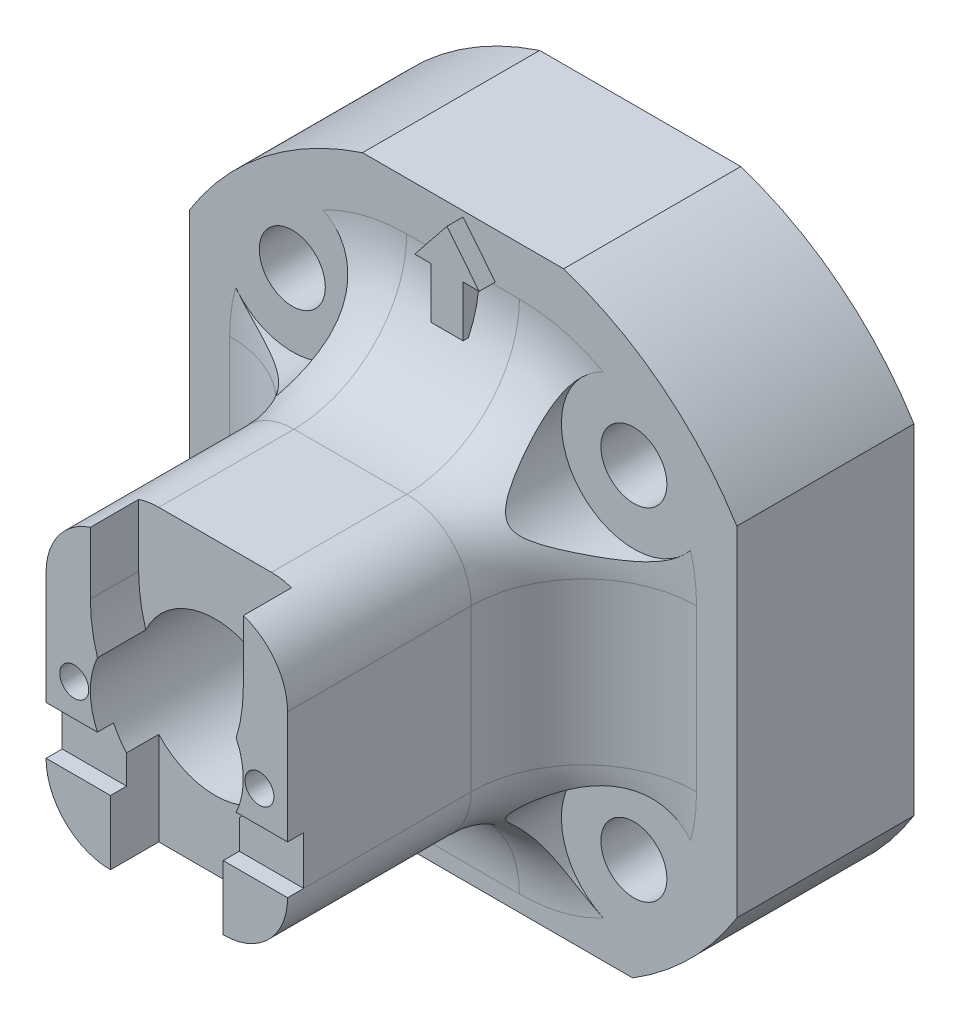
SolidWorks part; units mm, degrees
ref_plane "Front Plane" through (0, 0, 0) normal (0, 0, 1) x (1, 0, 0)
ref_plane "Top Plane" through (0, 0, 0) normal (0, 1, 0) x (1, 0, 0)
ref_plane "Right Plane" through (0, 0, 0) normal (1, 0, 0) x (0, 0, -1)
sketch "Sketch1" plane through (0, 0, 0) normal (0, 0, 1) x (1, 0, 0)
  circle A0 centre (0, 0) radius 20
  circle A1 centre (0, 0) radius 4.75
  dimension "D1" = 9.5
  dimension "D2" = 40
extrude "Boss-Extrude1" add sketch "Sketch1" along normal blind 11
sketch "Sketch2" plane through (0, 0, 11) normal (0, 0, 1) x (1, 0, 0)
  line L0 (0, 0) -> (0, 19) construction
  line L1 (-6.5933, 20) -> (6.5933, 20)
  line L2 (-6.5933, 20) -> (-6.5933, 19)
  line L3 (-6.5933, 19) -> (6.5933, 19)
  line L4 (6.5933, 20) -> (6.5933, 19)
  line L6 (-20, 15.8908) -> (-17, 15.8908)
  line L7 (-20, 15.8908) -> (-20, -10.5357)
  line L8 (-20, -10.5357) -> (-17, -10.5357)
  line L9 (-17, 15.8908) -> (-17, -10.5357)
  line L10 (20, 11.7256) -> (17, 11.7256)
  line L11 (20, 11.7256) -> (20, -14.8962)
  line L12 (20, -14.8962) -> (17, -14.8962)
  line L13 (17, 11.7256) -> (17, -14.8962)
  line L14 (19.7919, -20) -> (-18.9444, -20)
  line L15 (19.7919, -20) -> (19.7919, -17)
  line L16 (19.7919, -17) -> (-18.9444, -17)
  line L17 (-18.9444, -20) -> (-18.9444, -17)
  circle A0 centre (0, 0) radius 20 construction
  dimension "D1" = 1
  dimension "D2" = 3
extrude "Cut-Extrude1" cut sketch "Sketch2" against normal through all
sketch "Sketch3" plane through (0, 0, 11) normal (0, 0, 1) x (1, 0, 0)
  circle A0 centre (10.6066, -10.6066) radius 2 construction
  circle A1 centre (10.6066, 10.6066) radius 2 construction
  circle A2 centre (-10.6066, -10.6066) radius 2 construction
  circle A3 centre (-10.6066, 10.6066) radius 2 construction
  circle A4 centre (10.6066, -10.6066) radius 2 construction
  circle A5 centre (10.6066, 10.6066) radius 2 construction
  circle A6 centre (-10.6066, -10.6066) radius 2 construction
  circle A7 centre (-10.6066, 10.6066) radius 2 construction
  circle A8 centre (-10.6066, -10.6066) radius 2.05
  circle A9 centre (-10.6066, 10.6066) radius 2.05
  circle A10 centre (10.6066, 10.6066) radius 2.05
  circle A11 centre (10.6066, -10.6066) radius 2.05
  dimension "D1" = 4.1
extrude "Cut-Extrude2" cut sketch "Sketch3" against normal through all
sketch "Sketch5" plane through (0, 0, 11) normal (0, 0, 1) x (1, 0, 0)
  line L4 (7.5, -5) -> (7.5, 5)
  line L5 (3.5, 9) -> (-3.5, 9)
  line L6 (-7.5, 5) -> (-7.5, -5)
  line L7 (-3.5, -9) -> (3.5, -9)
  line L8 (7.5, -5) -> (7.5, 5)
  line L9 (3.5, 9) -> (-3.5, 9)
  line L10 (-7.5, 5) -> (-7.5, -5)
  line L11 (-3.5, -9) -> (3.5, -9)
  circle A0 centre (-5.75, 0) radius 1.075 construction
  circle A1 centre (5.75, 0) radius 1.075 construction
  circle A2 centre (-5.75, 0) radius 1.075 construction
  circle A3 centre (5.75, 0) radius 1.075 construction
  circle A4 centre (-5.75, 0) radius 0.9
  circle A5 centre (5.75, 0) radius 0.9
  arc A8 (3.5, -9) -> (7.5, -5) centre (3.5, -5) ccw
  arc A9 (7.5, 5) -> (3.5, 9) centre (3.5, 5) ccw
  arc A10 (-3.5, 9) -> (-7.5, 5) centre (-3.5, 5) ccw
  arc A11 (-7.5, -5) -> (-3.5, -9) centre (-3.5, -5) ccw
  arc A12 (3.5, -9) -> (7.5, -5) centre (3.5, -5) ccw
  arc A13 (7.5, 5) -> (3.5, 9) centre (3.5, 5) ccw
  arc A14 (-3.5, 9) -> (-7.5, 5) centre (-3.5, 5) ccw
  arc A15 (-7.5, -5) -> (-3.5, -9) centre (-3.5, -5) ccw
  dimension "D2" = 1.8
  dimension "D1" = 0
extrude "Boss-Extrude2" add sketch "Sketch5" along normal up to surface (18.4 mm away)
sketch "Sketch13" plane through (0, 0, 11) normal (0, 0, 1) x (1, 0, 0)
  circle A0 centre (5.75, 0) radius 0.9 construction
  circle A1 centre (-5.75, 0) radius 0.9 construction
  circle A2 centre (5.75, 0) radius 0.9
  circle A3 centre (-5.75, 0) radius 0.9
extrude "Boss-Extrude3" add sketch "Sketch13" along normal offset from surface (8.4 mm away) 10 up to face at (5.75, -0.9, 29.4)
sketch "Sketch7" plane through (0, 0, 29.4) normal (0, 0, 1) x (1, 0, 0)
  line L1 (-8.8438, -2) -> (9.3839, -2)
  line L2 (-8.8438, -2) -> (-8.8438, -5)
  line L3 (-8.8438, -5) -> (9.3839, -5)
  line L4 (9.3839, -2) -> (9.3839, -5)
  dimension "D1" = 3
  dimension "D2" = 2
extrude "Cut-Extrude4" cut sketch "Sketch7" against normal blind 1
fillet "Fillet1" radius 7 8 edges at (-6.3284, 7.8284, 11) (0, 9, 11) (6.3284, 7.8284, 11) (7.5, 0, 11) (6.3284, -7.8284, 11) (0, -9, 11) (-6.3284, -7.8284, 11) (-7.5, 0, 11)
sketch "Sketch9" plane through (0, 0, 11) normal (0, 0, 1) x (1, 0, 0)
  circle A7 centre (10.6066, 10.6066) radius 2 construction
  circle A9 centre (-10.6066, 10.6066) radius 2 construction
  circle A11 centre (-10.6066, -10.6066) radius 2 construction
  circle A13 centre (10.6066, -10.6066) radius 2 construction
  circle A14 centre (10.6066, 10.6066) radius 4.5
  circle A15 centre (10.6066, -10.6066) radius 4.5
  circle A16 centre (-10.6066, -10.6066) radius 4.5
  circle A17 centre (-10.6066, 10.6066) radius 4.5
  arc A18 (-12.554, 11.247) -> (-11.6826, 12.3515) centre (-10.6066, 10.6066) ccw construction
  arc A19 (11.6826, 12.3515) -> (12.554, 11.247) centre (10.6066, 10.6066) ccw construction
  arc A20 (12.554, -11.247) -> (11.6826, -12.3515) centre (10.6066, -10.6066) ccw construction
  arc A21 (-11.6826, -12.3515) -> (-12.554, -11.247) centre (-10.6066, -10.6066) ccw construction
  dimension "D1" = 9
extrude "Cut-Extrude5" cut sketch "Sketch9" along normal through all
sketch "Sketch10" plane through (0, 0, 0) normal (0, 0, -1) x (-1, 0, 0)
  circle A0 centre (0, 0) radius 4.75 construction
  circle A1 centre (0, 0) radius 4.75
extrude "Cut-Extrude6" cut sketch "Sketch10" against normal through all
sketch "Sketch11" plane through (0, 9, 0) normal (0, 1, 0) x (1, 0, 0)
  line L1 (-4.75, -29.4) -> (4.75, -29.4)
  line L2 (-4.75, -29.4) -> (-4.75, -26.4)
  line L3 (-4.75, -26.4) -> (4.75, -26.4)
  line L4 (4.75, -29.4) -> (4.75, -26.4)
  line L5 (0, 0) -> (0, -26.4) construction
  line L6 (-6.245, 0) -> (6.245, 0) construction
  dimension "D1" = 3
  dimension "D2" = 9.5
extrude "Cut-Extrude7" cut sketch "Sketch11" against normal blind 7
sketch "Sketch12" plane through (0, 0, 0) normal (0, 0, -1) x (-1, 0, 0)
  circle A0 centre (0, 0) radius 6
  dimension "D1" = 12
extrude "Cut-Extrude8" cut sketch "Sketch12" against normal offset from surface (14.4 mm away) 15 up to face at (-5.6956, 2.3742, 29.4)
chamfer "Chamfer2" distance 1.5 angle 45 1 edges at (0, -6, 14.4)
chamfer "Chamfer1" distance 4 angle 50 1 edges at (-6, 0, 0) first distance on face at (-6, 0, 0)
fillet "Fillet2" radius 10 2 edges at (4.75, 2, 27.9) (-4.75, 2, 27.9)
sketch "Sketch14" plane through (0, -9, 0) normal (0, -1, 0) x (1, 0, 0)
  line L0 (3.5, 29.4) -> (3.5, 18) construction
  line L1 (-3.5, 29.4) -> (3.5, 29.4)
  line L2 (-3.5, 29.4) -> (-3.5, 26.4)
  line L3 (-3.5, 26.4) -> (3.5, 26.4)
  line L4 (3.5, 29.4) -> (3.5, 26.4)
  line L5 (3.5, 26.4) -> (-3.5, 26.4) construction
extrude "Cut-Extrude9" cut sketch "Sketch14" against normal blind 10
sketch "Sketch15" plane through (0, 0, 11) normal (0, 0, 1) x (1, 0, 0)
  line L0 (-1, 13.002) -> (1, 13.002)
  line L1 (1, 13.002) -> (1, 16.1642)
  line L2 (1, 16.1642) -> (2, 16.1642)
  line L3 (2, 16.1642) -> (0, 18.6642)
  line L4 (0, 18.6642) -> (-2, 16.1642)
  line L5 (-2, 16.1642) -> (-1, 16.1642)
  line L6 (-1, 16.1642) -> (-1, 13.002)
  line L7 (0, 0) -> (0, 13.002) construction
  dimension "D1" = 2
  dimension "D2" = 4
  dimension "D3" = 2.5
extrude "Boss-Extrude4" add sketch "Sketch15" along normal blind 1
